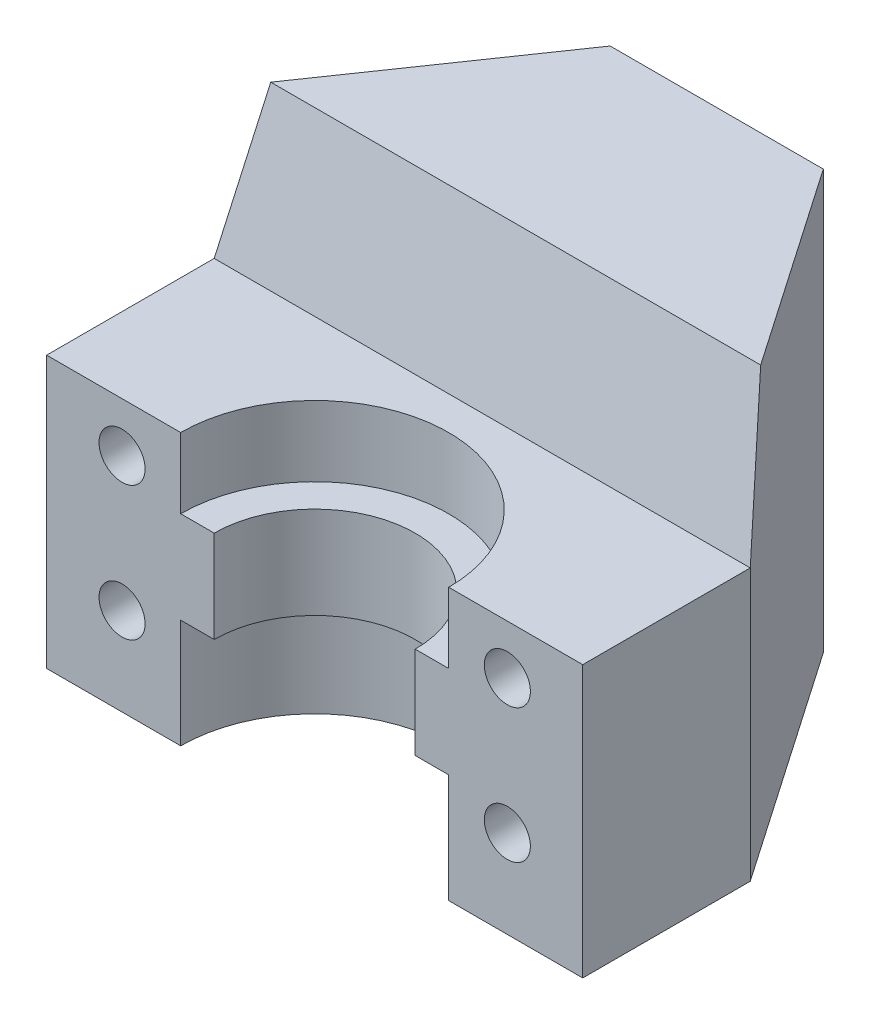
SolidWorks part; units mm, degrees
material "PLA"
ref_plane "Front Plane" through (0, 0, 0) normal (0, 0, 1) x (1, 0, 0)
ref_plane "Top Plane" through (0, 0, 0) normal (0, 1, 0) x (1, 0, 0)
ref_plane "Right Plane" through (0, 0, 0) normal (1, 0, 0) x (0, 0, -1)
sketch "Sketch1" plane through (0, 0, 0) normal (1, 0, 0) x (0, 0, -1)
  line L0 (0, 20) -> (12, 20) construction
  line L1 (0, 0) -> (12, 0)
  line L2 (0, 0) -> (0, 25)
  line L3 (0, 25) -> (12, 25)
  line L4 (12, 0) -> (12, 25)
  line L5 (0, 5) -> (12, 5) construction
  dimension "D1" = 15
  dimension "D2" = 12
  dimension "D3" = 25
  dimension "D4" = 5
extrude "Boss-Extrude1" add sketch "Sketch1" along normal mid plane 32 contours L4 L3 L2 L1
sketch "Sketch2" plane through (0, 0, 0) normal (0, 1, 0) x (1, 0, 0)
  line L0 (0, 0) -> (0, -2) construction
  line L1 (-16, -12) -> (16, -12)
  line L2 (-16, -12) -> (-16, -2)
  line L3 (-16, -2) -> (16, -2)
  line L4 (16, -12) -> (16, -2)
  line L5 (16, 0) -> (16, 12) construction
  dimension "D1" = 2
  dimension "D3" = 10
extrude "Boss-Extrude2" add sketch "Sketch2" along normal blind 16.2 separate body
sketch "Sketch3" plane through (16, 0, 0) normal (1, 0, 0) x (0, 0, -1)
  line L1 (-2, 0) -> (-2, 16.2) construction
  line L7 (0, 25) -> (0, 0) construction
  line L9 (-2, 0) -> (-2, 16.2)
  line L15 (0, 25) -> (0, 0)
  line L16 (0, 25) -> (-2, 16.2)
  line L17 (-2, 0) -> (0, 0)
extrude "Boss-Extrude3" add sketch "Sketch3" against normal up to surface (32 mm away) up to face at (-16, 8.1, 7)
hole_wizard "M5x0.8 Tapped Hole1" positions "Sketch7" profile "Sketch6" tap size "M5x0.8" standard "ANSI Metric"
sketch "Sketch7" plane through (0, 0, -12) normal (0, 0, -1) x (-1, 0, 0)
  line L0 (-16, 0) -> (16, 0) construction
  point P0 (0, 20)
  point P2 (0, 5)
  dimension "D1" = 15
  dimension "D2" = 5
sketch "Sketch6" plane through (0, 20, -12) normal (1, 0, 0) x (0, 1, 0)
  line L0 (0, 0) -> (0, 10.2618)
  line L1 (0, 10.2618) -> (2.1, 9)
  line L2 (2.1, 9) -> (2.1, 0)
  line L5 (2.1, 0) -> (0, 0)
  line L10 (0, 10.2618) -> (-2.1, 9) construction
  line L11 (0, -6.35) -> (0, 107.95) construction
  dimension "Tap Drill Dia." = 4.2
  dimension "Tap Drill Depth" = 9
  dimension "Drill Angle" = 118
cosmetic thread "Hole Thread1" parameters "D1"=4.2, "D2"=5
cosmetic thread "Hole Thread2" parameters "D1"=4.2, "D2"=5
sketch "Sketch9" plane through (0, 0, 0) normal (1, 0, 0) x (0, 0, -1)
  line L0 (-12, 16.2) -> (-4, 16.2)
  line L1 (-12, 16.2) -> (-12, 0) construction
  line L2 (-4, 16.2) -> (-4, 12)
  line L3 (-4, 12) -> (-6, 12)
  line L4 (-6, 12) -> (-6, 6.5)
  line L5 (-6, 6.5) -> (-4, 6.5)
  line L6 (-4, 6.5) -> (-4, 0)
  line L7 (-12, 0) -> (12, 0) construction
  line L8 (-4, 0) -> (-12, 0)
  line L9 (-12, 0) -> (-12, 16.2)
  line L10 (-12, 16.2) -> (-2, 16.2) construction
  dimension "D1" = 6
  dimension "D2" = 8
  dimension "D3" = 8
  dimension "D4" = 6.5
  dimension "D5" = 5.5
revolve "Cut-Revolve1" cut sketch "Sketch9" angle 360 about L9
sketch "Sketch10" plane through (0, 25, 0) normal (0, 1, 0) x (1, 0, 0)
  line L5 (16, -2) -> (16, 0) construction
  line L6 (-16, -2) -> (-6.3625, 12)
  line L7 (16, 12) -> (-16, 12) construction
  line L8 (-6.3625, 12) -> (-16, 12)
  line L9 (-16, 12) -> (-16, -2)
  line L10 (16, 12) -> (6.3625, 12)
  line L11 (16, -2) -> (16, 0)
  line L12 (6.3625, 12) -> (16, -2)
  line L13 (16, 12) -> (16, -2)
  line L14 (0, 0) -> (0, 12) construction
  line L15 (16, 0) -> (-16, 0) construction
  line M4 (-16, 12) -> (-16, 0)
  line M5 (-16, 0) -> (16, 0)
  line M6 (16, 0) -> (16, 12)
  line M7 (16, 12) -> (-16, 12)
  dimension "D1" = 12.725
extrude "Cut-Extrude2" cut sketch "Sketch10" against normal up to next contours L12 M7 M5 M6 | L12 L11 M5 | L6 M5 M7 M4 | L9 L6 M5 region at (-15.5411, 25, 0.6667) region at (-12.7301, 25, -7.5) region at (15.5411, 25, 0.6667) region at (12.7301, 25, -7.5)
hole_wizard "M3x0.5 Tapped Hole1" positions "Sketch12" profile "Sketch11" tap size "M3x0.5" standard "ANSI Metric"
sketch "Sketch12" plane through (0, 0, 12) normal (0, 0, 1) x (1, 0, 0)
  line L0 (0, 0) -> (0, 16.2) construction
  line L1 (8, 16.2) -> (-8, 16.2) construction
  line L4 (-11.5, 13.25) -> (-11.5, 5.25) construction
  line L7 (-11.5, 9.25) -> (0, 9.25) construction
  line L10 (-6, 6.5) -> (-6, 12) construction
  point P0 (-11.5, 13.25)
  point P2 (11.5, 13.25)
  point P7 (-11.5, 5.25)
  point P8 (11.5, 5.25)
  point P36 (-6, 9.25)
  dimension "D1" = 8
  dimension "D2" = 23
sketch "Sketch11" plane through (-11.5, 13.25, 12) normal (1, 0, 0) x (0, -1, 0)
  line L0 (0, 0) -> (0, 12.8262)
  line L1 (0, 12.8262) -> (1.375, 12)
  line L2 (1.375, 12) -> (1.375, 0)
  line L5 (1.375, 0) -> (0, 0)
  line L10 (0, 12.8262) -> (-1.375, 12) construction
  line L11 (0, -6.35) -> (0, 107.95) construction
  dimension "Tap Drill Dia." = 2.75
  dimension "Tap Drill Depth" = 12
  dimension "Drill Angle" = 118
cosmetic thread "Hole Thread3" parameters "D1"=6, "D2"=3
cosmetic thread "Hole Thread4" parameters "D1"=6, "D2"=3
cosmetic thread "Hole Thread5" parameters "D1"=6, "D2"=3
cosmetic thread "Hole Thread6" parameters "D1"=6, "D2"=3
